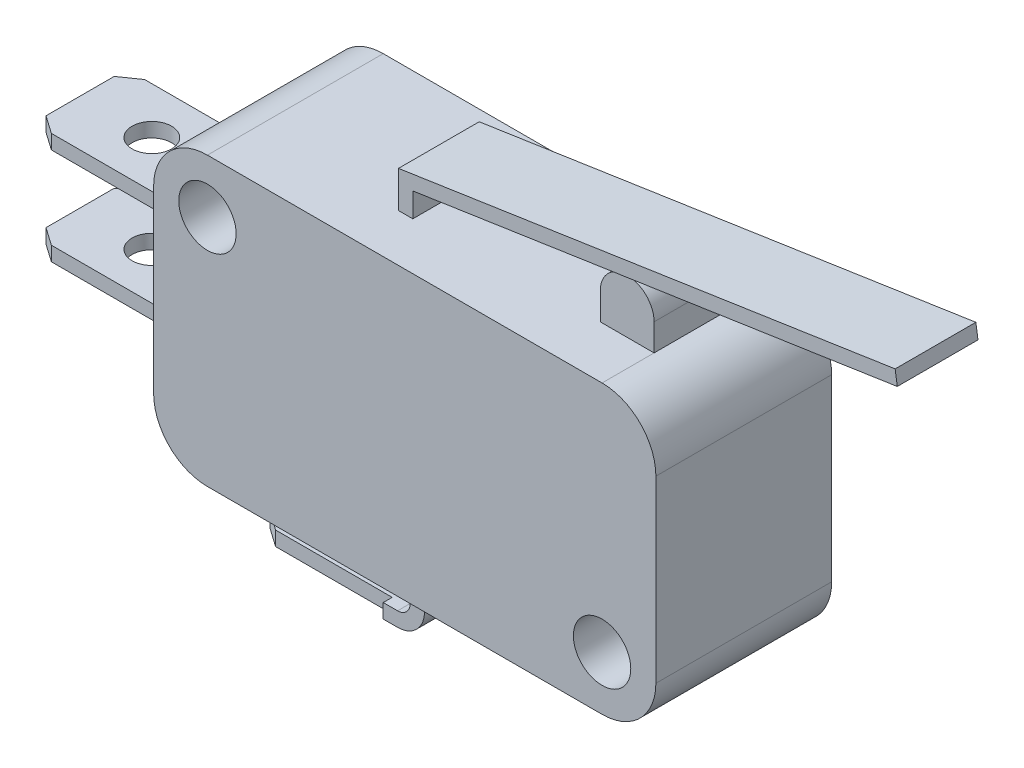
SolidWorks part; units mm, degrees
material "1060 合金"
ref_plane "前视基准面" through (0, 0, 0) normal (0, 0, 1) x (1, 0, 0)
ref_plane "上视基准面" through (0, 0, 0) normal (0, 1, 0) x (1, 0, 0)
ref_plane "右视基准面" through (0, 0, 0) normal (1, 0, 0) x (0, 0, -1)
sketch "草图1" plane through (0, 0, 0) normal (0, 0, 1) x (1, 0, 0)
  line L1 (-14, -8) -> (14, -8)
  line L2 (-14, -8) -> (-14, 8)
  line L3 (-14, 8) -> (14, 8)
  line L4 (14, -8) -> (14, 8)
  line L5 (-14, -8) -> (14, 8) construction
  line L6 (-14, 8) -> (14, -8) construction
  point P0 (0, 0)
  dimension "D1" = 28
  dimension "D2" = 16
extrude "凸台-拉伸1" add sketch "草图1" along normal mid plane 9.8
sketch "草图2" plane through (0, 0, 0) normal (0, 0, 1) x (1, 0, 0)
  line L0 (8, 8) -> (11, 8)
  line L1 (14, 8) -> (-14, 8) construction
  line L2 (11, 8) -> (11, 9.5)
  line L3 (8, 8) -> (8, 9.5)
  line L4 (14, -8) -> (14, 8) construction
  arc A0 (8, 9.5) -> (11, 9.5) centre (9.5, 9.5) cw
  dimension "D1" = 3
  dimension "D2" = 1.5
  dimension "D3" = 3
extrude "凸台-拉伸2" add sketch "草图2" along normal mid plane 4
sketch "草图3" plane through (-14, 0, 0) normal (-1, 0, 0) x (0, 0, 1)
  line L0 (4.9, -8) -> (-4.9, -8) construction
  line L1 (-3.1, 1.6) -> (3.1, 1.6)
  line L2 (-3.1, 1.6) -> (-3.1, 2.4)
  line L3 (-3.1, 2.4) -> (3.1, 2.4)
  line L4 (3.1, 1.6) -> (3.1, 2.4)
  line L5 (-3.1, 1.6) -> (3.1, 2.4) construction
  line L6 (-3.1, 2.4) -> (3.1, 1.6) construction
  line L7 (-3.1, -3.8) -> (3.1, -3.8)
  line L8 (-3.1, -3.8) -> (-3.1, -3)
  line L9 (-3.1, -3) -> (3.1, -3)
  line L10 (3.1, -3.8) -> (3.1, -3)
  line L11 (-3.1, -3.8) -> (3.1, -3) construction
  line L12 (-3.1, -3) -> (3.1, -3.8) construction
  point P0 (0, 2)
  point P5 (0, -3.4)
  dimension "D1" = 0.8
  dimension "D2" = 0.8
  dimension "D3" = 4.6
  dimension "D4" = 4.2
  dimension "D5" = 6.2
extrude "凸台-拉伸3" add sketch "草图3" along normal blind 9
sketch "草图4" plane through (0, 2.4, 0) normal (0, 1, 0) x (1, 0, 0)
  line L0 (-23, -3.1) -> (-23, 3.1) construction
  line L1 (-15.5, 3.1) -> (-15.5, 2.6)
  line L2 (-23, 3.1) -> (-14, 3.1) construction
  line L3 (-15.5, 2.6) -> (-22, 2.6)
  line L4 (-22, 2.6) -> (-23, 1.9)
  line L5 (-23, 1.9) -> (-23, 3.1)
  line L6 (-23, 3.1) -> (-15.5, 3.1)
  line L7 (-26.2882, 0) -> (-14.6131, 0) construction
  line L8 (-23, -3.1) -> (-15.5, -3.1)
  line L9 (-23, -1.9) -> (-23, -3.1)
  line L10 (-22, -2.6) -> (-23, -1.9)
  line L11 (-15.5, -2.6) -> (-22, -2.6)
  line L12 (-15.5, -3.1) -> (-15.5, -2.6)
  circle A0 centre (-19, 0) radius 1.1
  point P4 (-23, 0)
  dimension "D1" = 2.2
  dimension "D2" = 4
  dimension "D3" = 0.5
  dimension "D4" = 7.5
  dimension "D5" = 6.5
  dimension "D6" = 1.2
extrude "切除-拉伸1" cut sketch "草图4" against normal through all
sketch "草图5" plane through (0, 0, 0) normal (0, 0, 1) x (1, 0, 0)
  line L0 (-1.5, -8) -> (-0.7, -8)
  line L1 (-14, -8) -> (14, -8) construction
  line L2 (-0.7, -8) -> (-0.7, -9.8)
  line L3 (-2.2, -11.3) -> (-10.5, -11.3)
  line L4 (-10.5, -11.3) -> (-10.5, -10.5)
  line L5 (-10.5, -10.5) -> (-2.2, -10.5)
  line L6 (-1.5, -9.8) -> (-1.5, -8)
  line L7 (-14, 8) -> (-14, -8) construction
  arc A0 (-0.7, -9.8) -> (-2.2, -11.3) centre (-2.2, -9.8) cw
  arc A1 (-2.2, -10.5) -> (-1.5, -9.8) centre (-2.2, -9.8) ccw
  point P14 (-1.5, -10.5)
  dimension "D6" = 1.5
  dimension "D7" = 0.7
  dimension "D1" = 0.8
  dimension "D2" = 0.8
  dimension "D3" = 2.5
  dimension "D4" = 9
  dimension "D5" = 12.5
extrude "凸台-拉伸4" add sketch "草图5" along normal mid plane 6.2
sketch "草图6" plane through (0, -11.3, 0) normal (0, -1, 0) x (1, 0, 0)
  line L0 (-3, 3.1) -> (-3, 2.6)
  line L1 (-3, 2.6) -> (-9.5, 2.6)
  line L2 (-9.5, 2.6) -> (-10.5, 1.9)
  line L3 (-10.5, 1.9) -> (-10.5, 3.1)
  line L4 (-10.5, 3.1) -> (-3, 3.1)
  line L5 (-11.7822, 0) -> (-0.1072, 0) construction
  line L6 (-10.5, -3.1) -> (-3, -3.1)
  line L7 (-10.5, -1.9) -> (-10.5, -3.1)
  line L8 (-9.5, -2.6) -> (-10.5, -1.9)
  line L9 (-3, -2.6) -> (-9.5, -2.6)
  line L10 (-3, -3.1) -> (-3, -2.6)
  line L11 (-10.5, 3.1) -> (-2.2, 3.1) construction
  line L12 (-10.5, 3.1) -> (-10.5, -3.1) construction
  circle A0 centre (-6.5, 0) radius 1.1
  point P18 (-10.5, 0)
  dimension "D1" = 2.2
  dimension "D6" = 4
  dimension "D2" = 0.5
  dimension "D3" = 7.5
  dimension "D4" = 6.5
  dimension "D5" = 1.2
extrude "切除-拉伸2" cut sketch "草图6" against normal up to next
sketch "草图7" plane through (0, 0, 0) normal (0, 0, 1) x (1, 0, 0)
  line L0 (-3, 8) -> (-2.2, 8)
  line L1 (14, 8) -> (-14, 8) construction
  line L2 (-2.2, 8) -> (-2.2, 9.3469)
  line L3 (-2.2, 9.3469) -> (24.8076, 13.4089)
  line L4 (24.8076, 13.4089) -> (24.6886, 14.2)
  line L5 (24.6886, 14.2) -> (-3, 10.0356)
  line L6 (-3, 10.0356) -> (-3, 8)
  line L7 (-14, 8) -> (-14, -8) construction
  dimension "D1" = 0.8
  dimension "D2" = 0.8
  dimension "D3" = 11
  dimension "D4" = 28
  dimension "D5" = 6.2
extrude "凸台-拉伸10" add sketch "草图7" along normal mid plane 4.5 contours L5 L6 L0 L2 L3 L4
fillet "圆角1" radius 3 4 edges at (14, 8, 0) (14, -8, 0) (-14, -8, 0) (-14, 8, 0)
sketch "草图8" plane through (0, 0, 4.9) normal (0, 0, 1) x (1, 0, 0)
  line L0 (-14, 5) -> (-14, -5) construction
  line L1 (11, 8) -> (-11, 8) construction
  circle A0 centre (-11, 5) radius 1.6
  circle A1 centre (11, -5) radius 1.6
  point P10 (0, 0)
  dimension "D1" = 3.2
  dimension "D2" = 3
  dimension "D3" = 3
  dimension "D4" = 2
extrude "切除-拉伸3" cut sketch "草图8" against normal through all
